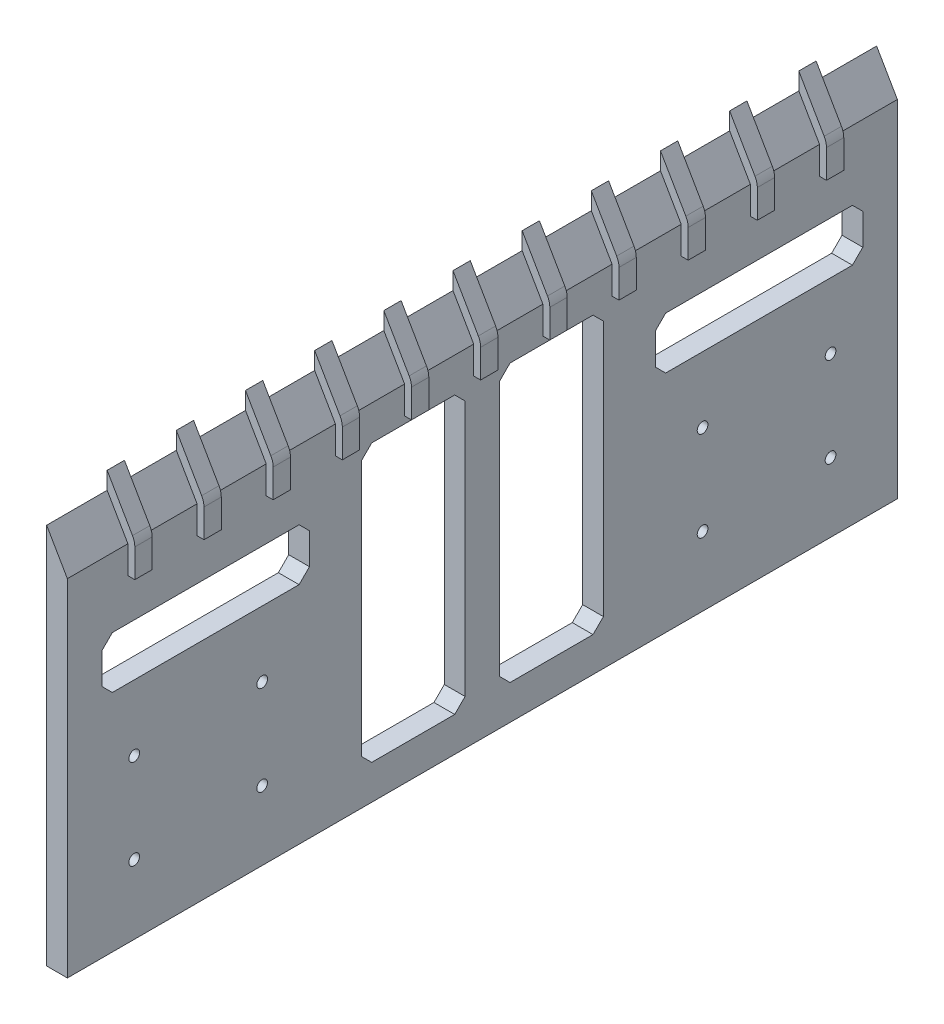
SolidWorks part; units mm, degrees
ref_plane "前视基准面" through (0, 0, 0) normal (0, 0, 1) x (1, 0, 0)
ref_plane "上视基准面" through (0, 0, 0) normal (0, 1, 0) x (1, 0, 0)
ref_plane "右视基准面" through (0, 0, 0) normal (1, 0, 0) x (0, 0, -1)
sketch "草图1" plane through (0, 0, 0) normal (1, 0, 0) x (0, 0, -1)
  line L1 (0, 0) -> (240, 0)
  line L2 (0, 0) -> (0, -100)
  line L3 (0, -100) -> (240, -100)
  line L4 (240, 0) -> (240, -100)
  dimension "D1" = 240
  dimension "D2" = 100
extrude "凸台-拉伸1" add sketch "草图1" along normal blind 6
sketch "草图2" plane through (6, 0, 0) normal (1, 0, 0) x (0, 0, -1)
  line L0 (0, 0) -> (0, -100) construction
  line L1 (19.3235, -54) -> (56.3235, -54) construction
  line L2 (19.3235, -54) -> (19.3235, -80) construction
  line L3 (19.3235, -80) -> (56.3235, -80) construction
  line L4 (56.3235, -54) -> (56.3235, -80) construction
  line L5 (240, 0) -> (0, 0) construction
  line L6 (120, 0) -> (120, -100) construction
  line L7 (0, -100) -> (240, -100) construction
  line L8 (183.6765, -54) -> (183.6765, -80) construction
  line L9 (220.6765, -80) -> (183.6765, -80) construction
  line L10 (220.6765, -54) -> (220.6765, -80) construction
  line L11 (220.6765, -54) -> (183.6765, -54) construction
  circle A0 centre (19.3235, -54) radius 1.55
  circle A1 centre (56.3235, -80) radius 1.55
  circle A2 centre (56.3235, -54) radius 1.55
  circle A3 centre (19.3235, -80) radius 1.55
  circle A4 centre (220.6765, -80) radius 1.55
  circle A5 centre (183.6765, -54) radius 1.55
  circle A6 centre (183.6765, -80) radius 1.55
  circle A7 centre (220.6765, -54) radius 1.55
  dimension "D5" = 3.1
  dimension "D1" = 19.3235
  dimension "D2" = 54
  dimension "D3" = 37
  dimension "D4" = 26
extrude "切除-拉伸1" cut sketch "草图2" against normal through all
sketch "草图3" plane through (6, 0, 0) normal (1, 0, 0) x (0, 0, -1)
  line L0 (120, 0) -> (120, -100) construction
  line L1 (10, -20) -> (70, -20)
  line L2 (10, -20) -> (10, -35)
  line L3 (10, -35) -> (70, -35)
  line L4 (70, -20) -> (70, -35)
  line L5 (240, 0) -> (0, 0) construction
  line L6 (0, -100) -> (240, -100) construction
  line L7 (0, 0) -> (0, -100) construction
  line L8 (170, -20) -> (170, -35)
  line L9 (230, -35) -> (170, -35)
  line L10 (230, -20) -> (230, -35)
  line L11 (230, -20) -> (170, -20)
  dimension "D1" = 10
  dimension "D2" = 20
  dimension "D3" = 15
  dimension "D4" = 60
extrude "切除-拉伸2" cut sketch "草图3" against normal through all
sketch "草图4" plane through (6, 0, 0) normal (1, 0, 0) x (0, 0, -1)
  line L0 (120, 0) -> (120, -100) construction
  line L1 (85, -10) -> (115, -10)
  line L2 (85, -10) -> (85, -90)
  line L3 (85, -90) -> (115, -90)
  line L4 (115, -10) -> (115, -90)
  line L5 (240, 0) -> (0, 0) construction
  line L6 (0, -100) -> (240, -100) construction
  line L7 (0, 0) -> (0, -100) construction
  line L8 (125, -10) -> (125, -90)
  line L9 (155, -90) -> (125, -90)
  line L10 (155, -10) -> (155, -90)
  line L11 (155, -10) -> (125, -10)
  dimension "D1" = 10
  dimension "D2" = 10
  dimension "D3" = 85
  dimension "D4" = 30
extrude "切除-拉伸3" cut sketch "草图4" against normal through all contours L4 L1 L2 L3 | L8 L9 L10 L11 region at (6, -50, -100)
sketch "草图5" plane through (0, 0, 0) normal (-1, 0, 0) x (0, 0, 1)
  circle A0 centre (-183.6765, -80) radius 3
  circle A1 centre (-220.6765, -80) radius 3
  circle A2 centre (-183.6765, -54) radius 3
  circle A3 centre (-220.6765, -54) radius 3
  circle A4 centre (-45, -80) radius 3
  circle A5 centre (-19.3235, -80) radius 3
  circle A6 centre (-19.3235, -54) radius 3
  circle A7 centre (-56.3235, -54) radius 3
  dimension "D1" = 6
extrude "切除-拉伸4" cut sketch "草图5" against normal blind 3
sketch "草图6" plane through (0, 0, 0) normal (0, 0, 1) x (1, 0, 0)
  line L0 (6, 0) -> (0, 0)
  line L1 (0, 0) -> (0, 10.3923)
  line L2 (0, 10.3923) -> (6, 0)
  dimension "D1" = 30
extrude "凸台-拉伸2" add sketch "草图6" against normal blind 240
ref_plane "基准面1" through (0, 0, -117.5) normal (0, 0, 1) x (1, 0, 0)
sketch "草图7" plane through (0, 0, -117.5) normal (0, 0, 1) x (1, 0, 0)
  line L0 (0, 10.3923) -> (0, 15.3923)
  line L1 (0, 15.3923) -> (8, 1.5359)
  line L2 (8, 1.5359) -> (8, -8)
  line L3 (8, -8) -> (6, -8)
  line L4 (6, 0) -> (6, -100) construction
  line L5 (6, -8) -> (6, 0)
  line L6 (6, 0) -> (0, 10.3923)
  dimension "D1" = 5
  dimension "D2" = 2
  dimension "D3" = 8
extrude "凸台-拉伸3" add sketch "草图7" against normal blind 5
pattern_linear "阵列(线性)5" count 6 spacing 20 along (0, 0, 1) count 6 spacing 20 along (0, 0, -1) of "凸台-拉伸3"
fillet "圆角5" radius 5 11 edges at (8, 1.5359, -20) (8, 1.5359, -40) (8, 1.5359, -60) (8, 1.5359, -80) (8, 1.5359, -100) (8, 1.5359, -120) (8, 1.5359, -140) (8, 1.5359, -160) (8, 1.5359, -180) (8, 1.5359, -200) (8, 1.5359, -220)
chamfer "倒角1" distance 3 angle 45 16 edges at (3, -90, -85) (3, -90, -125) (3, -35, -170) (3, -35, -230) (3, -90, -155) (3, -90, -115) (3, -20, -230) (3, -10, -155) (3, -10, -115) (3, -20, -170) (3, -10, -125) (3, -10, -85) (3, -35, -70) (3, -20, -70) (3, -35, -10) (3, -20, -10)
